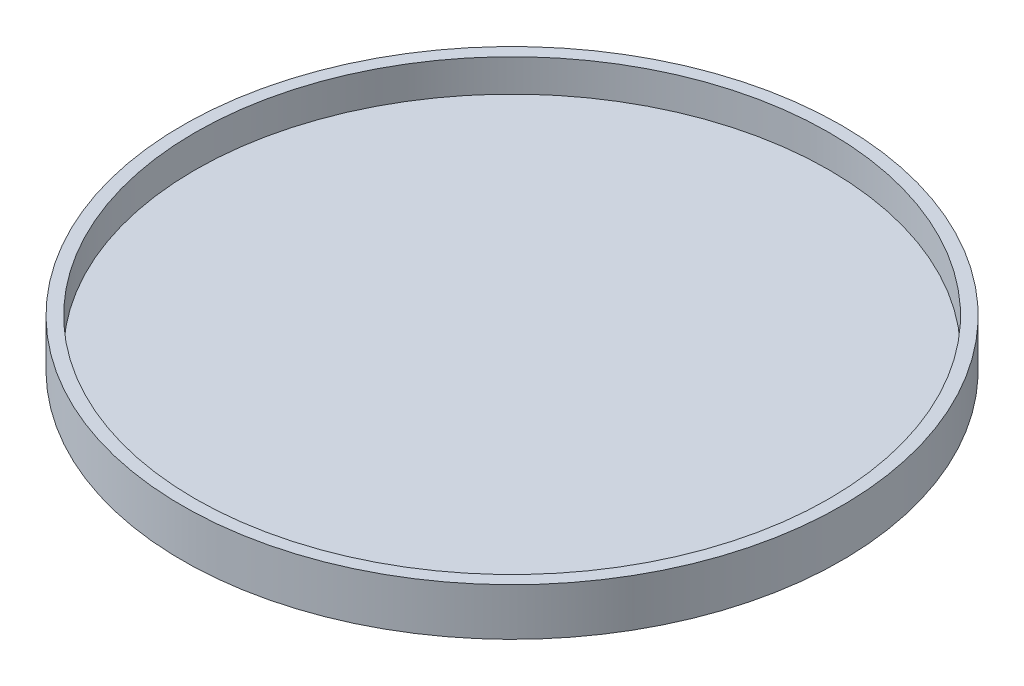
SolidWorks part; units mm, degrees
ref_plane "Front Plane" through (0, 0, 0) normal (0, 0, 1) x (1, 0, 0)
ref_plane "Top Plane" through (0, 0, 0) normal (0, 1, 0) x (1, 0, 0)
ref_plane "Right Plane" through (0, 0, 0) normal (1, 0, 0) x (0, 0, -1)
sketch "Sketch1" plane through (0, 0, 0) normal (0, 1, 0) x (1, 0, 0)
  circle A0 centre (0, 0) radius 63.625
  circle A1 centre (0, 0) radius 66.125
  dimension "D1" = 127.25
  dimension "D2" = 2.5
extrude "Boss-Extrude1" add sketch "Sketch1" along normal blind 6.5
extrude "Boss-Extrude2" add sketch "Sketch1<2>" against normal blind 3 contours A1
sketch "Sketch1<2>" plane through (0, 0, 0) normal (0, 1, 0) x (1, 0, 0) same geometry as "Sketch1"
sketch "Sketch2" plane through (0, -3, 0) normal (0, -1, 0) x (1, 0, 0)
  line L0 (-8.75, 37.5623) -> (8.75, 37.5623)
  line L1 (-11.0595, 37.5623) -> (11.0595, 37.5623)
  line L2 (-17.5, 26) -> (17.5, 26)
  line L3 (36.9049, -11.2034) -> (28.1549, -26.3589)
  line L4 (38.0597, -9.2034) -> (27.0002, -28.359)
  line L5 (31.2667, 2.1554) -> (13.7667, -28.1554)
  line L6 (-28.1549, -26.3589) -> (-36.9049, -11.2034)
  line L7 (-27.0002, -28.359) -> (-38.0597, -9.2034)
  line L8 (-13.7667, -28.1554) -> (-31.2667, 2.1554)
  circle A0 centre (0, 26) radius 14.5
  circle A1 centre (0, 26) radius 16
  circle A2 centre (-17.5, 26) radius 4
  circle A3 centre (17.5, 26) radius 4
  circle A4 centre (-17.5, 26) radius 2.05
  circle A5 centre (17.5, 26) radius 2.05
  circle A6 centre (22.5167, -13) radius 14.5
  circle A7 centre (22.5167, -13) radius 16
  circle A8 centre (31.2667, 2.1554) radius 4
  circle A9 centre (13.7667, -28.1554) radius 4
  circle A10 centre (31.2667, 2.1554) radius 2.05
  circle A11 centre (13.7667, -28.1554) radius 2.05
  circle A12 centre (-22.5167, -13) radius 14.5
  circle A13 centre (-22.5167, -13) radius 16
  circle A14 centre (-13.7667, -28.1554) radius 4
  circle A15 centre (-31.2667, 2.1554) radius 4
  circle A16 centre (-13.7667, -28.1554) radius 2.05
  circle A17 centre (-31.2667, 2.1554) radius 2.05
  point P43 (0, 0)
  dimension "D1" = 29
  dimension "D3" = 32
  dimension "D4" = 8
  dimension "D7" = 4.1
  dimension "D2" = 17.5
  dimension "D5" = 35
  dimension "D6" = 17.5
  dimension "D8" = 26
  dimension "D9" = 3
extrude "Boss-Extrude3" add sketch "Sketch2" along normal blind 17 contours A11 A7 A9 | A9 A7 L4 A6 | A11 A7 A9 A6 L5 | A11 L5 A6 A9 A7 | A9 A6 A8 A7 | A10 L5 A6 A8 A7 | A10 A7 A8 A6 L5 | A10 A7 A8 | A16 A13 A14 | A15 A12 A14 A13 | A16 L8 A12 A14 A13 | A16 A13 A14 A12 L8 | A8 A6 L4 A7 | A14 A12 L7 A13 | A15 A13 L7 A12 | A17 A13 A15 | A17 A13 A15 A12 L8 | A17 L8 A12 A15 A13 | A3 A0 A2 A1 | A4 A1 A2 A0 L2 | A4 L2 A0 A2 A1 | A4 A1 A2 | A3 A1 L1 A0 | A2 A0 L1 A1 | A5 L2 A0 A3 A1 | A5 A1 A3 A0 L2 | A5 A1 A3 region at (-12.8909, -3, 33.5732) region at (12.8909, -3, 33.5732) region at (-15.1211, -3, 27.667) region at (15.1211, -3, 27.667) region at (-15.9118, -3, 28.4503) region at (-15.1211, -3, 24.333) region at (19.5019, -3, 29.3478) region at (15.1211, -3, 24.333) region at (-14.6703, -3, 22.7087) region at (35.5207, -3, -5.6227) region at (22.6298, -3, -27.9504) region at (31.5209, -3, -0.7383) region at (16.3998, -3, -26.9287) region at (32.6006, -3, -0.4376) region at (28.6335, -3, 0.9287) region at (11.8211, -3, -31.5252) region at (13.5124, -3, -25.2617) region at (9.6575, -3, -5.5758) region at (-22.6298, -3, -27.9504) region at (-35.5207, -3, -5.6227) region at (-16.3998, -3, -26.9287) region at (-31.5209, -3, -0.7383) region at (-16.6793, -3, -28.0141) region at (-13.5124, -3, -25.2617) region at (-33.2122, -3, 5.5252) region at (-28.6335, -3, 0.9287) region at (-9.0854, -3, -19.3307)
fillet "Fillet2" radius 4 15 edges at (-13.9259, -3, 33.8783) (-21.5, -3, 26) (0, -3, 10) (13.9259, -3, 33.8783) (21.5, -3, 26) (36.3025, -3, -4.8789) (33.2667, -3, 5.6195) (8.6603, -3, -5) (11.7667, -3, -31.6195) (22.3765, -3, -28.9994) (-36.3025, -3, -4.8789) (-33.2667, -3, 5.6195) (-22.3765, -3, -28.9994) (-11.7667, -3, -31.6195) (-8.6603, -3, -5)
